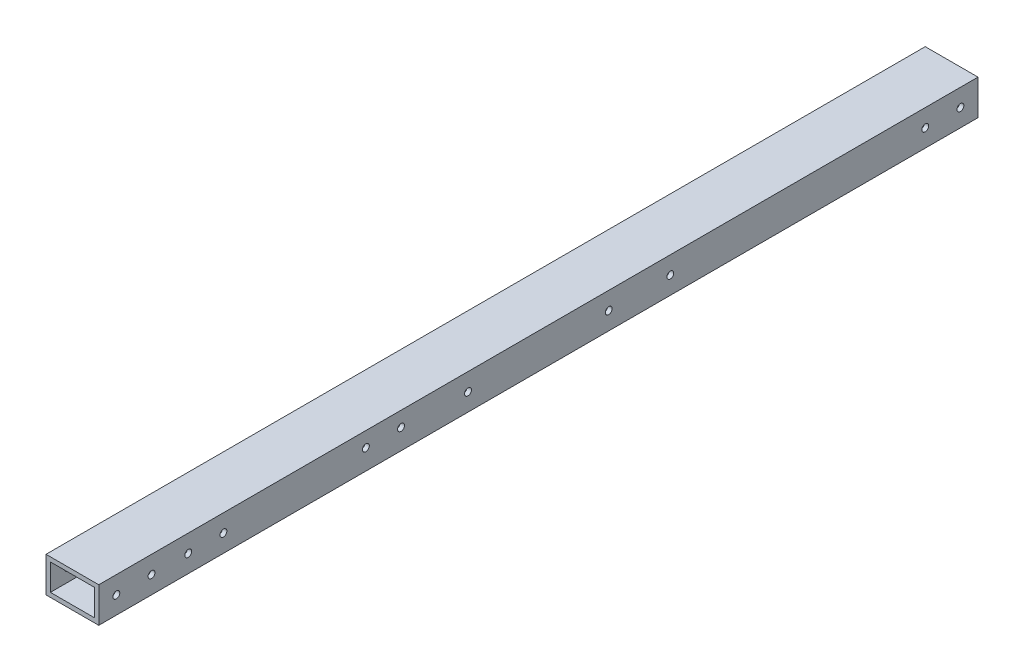
SolidWorks part; units mm, degrees
material "1060 Alloy"
ref_plane "Front Plane" through (0, 0, 0) normal (0, 0, 1) x (1, 0, 0)
ref_plane "Top Plane" through (0, 0, 0) normal (0, 1, 0) x (1, 0, 0)
ref_plane "Right Plane" through (0, 0, 0) normal (1, 0, 0) x (0, 0, -1)
sketch "Sketch1" plane through (0, 0, 0) normal (0, 0, 1) x (1, 0, 0)
  line L0 (-15.875, 9.525) -> (15.875, 9.525)
  line L2 (-19.05, 12.7) -> (19.05, 12.7)
  line L3 (-19.05, 12.7) -> (-19.05, -12.7)
  line L4 (-19.05, -12.7) -> (19.05, -12.7)
  line L5 (19.05, 12.7) -> (19.05, -12.7)
  line L10 (15.875, 9.525) -> (15.875, -9.525)
  line L11 (-15.875, -9.525) -> (15.875, -9.525)
  line L12 (-15.875, 9.525) -> (-15.875, -9.525)
  point P12 (0, 12.7)
  point P14 (19.05, 0)
  dimension "Wall Thickness" = 3.175
  dimension "Outside Width" = 38.1
  dimension "Outside Height" = 25.4
  dimension "Inside Height" = 19.05
  dimension "Inside Width" = 31.75
sketch "Sketch2" plane through (0, 0, 0) normal (1, 0, 0) x (0, 0, -1)
  line L0 (317.5, 0) -> (-317.5, 0)
  point P4 (0, 0)
  point P7 (-317.5, 0)
  point P10 (317.5, 0)
  dimension "Length" = 635
sketch "Sketch3" plane through (0, 0, 0) normal (0, 0, 1) x (1, 0, 0)
  line L21 (19.05, 12.7) -> (-19.05, 12.7)
  line L22 (19.05, -12.7) -> (19.05, 12.7)
  line L23 (-19.05, -12.7) -> (19.05, -12.7)
  line L24 (-19.05, 12.7) -> (-19.05, -12.7)
  line L25 (19.05, 12.7) -> (-19.05, 12.7)
  line L26 (19.05, -12.7) -> (19.05, 12.7)
  line L27 (-19.05, -12.7) -> (19.05, -12.7)
  line L28 (-19.05, 12.7) -> (-19.05, -12.7)
  line L29 (15.875, 9.525) -> (-15.875, 9.525)
  line L30 (15.875, -9.525) -> (15.875, 9.525)
  line L31 (-15.875, -9.525) -> (15.875, -9.525)
  line L32 (-15.875, 9.525) -> (-15.875, -9.525)
  line L33 (15.875, 9.525) -> (-15.875, 9.525)
  line L34 (15.875, -9.525) -> (15.875, 9.525)
  line L35 (-15.875, -9.525) -> (15.875, -9.525)
  line L36 (-15.875, 9.525) -> (-15.875, -9.525)
  dimension "D1" = 0
  dimension "D2" = 0
extrude "Boss-Extrude1" add sketch "Sketch3" along normal up to vertex (317.5 mm away) and the other way up to vertex (317.5 mm away) up to point (0, 0, 317.5) other way up to point (0, 0, -317.5)
sketch "Drawing Reference" plane through (0, 0, 0) normal (1, 0, 0) x (0, 0, -1)
  line L0 (-317.5, 0) -> (317.5, 0) construction
  line L1 (0, -12.7) -> (0, 12.7) construction
  line L2 (-317.5, -12.7) -> (317.5, -12.7) construction
  line L5 (-317.5, 12.7) -> (317.5, 12.7) construction
  point P7 (-290.068, 0)
  point P8 (290.068, 0)
  dimension "D1" = 27.432
sketch "Sketch4" plane through (-19.05, 0, 0) normal (-1, 0, 0) x (0, 0, 1)
  line L0 (-317.5, 0) -> (-304.8, 0)
  line L1 (-317.5, 12.7) -> (-317.5, -12.7) construction
  line L2 (-304.8, 0) -> (-279.4, 0)
  line L3 (317.5, 12.7) -> (317.5, -12.7) construction
  line L4 (317.5, 0) -> (304.8, 0)
  line L5 (304.8, 0) -> (279.4, 0)
  line L6 (0, 0) -> (50.8, 0) construction
  line L7 (0, 0) -> (-50.8, 0) construction
  point P11 (-304.8, 0)
  point P13 (-279.4, 0)
  point P14 (304.8, 0)
  point P15 (279.4, 0)
hole_wizard "#10 Clearance Hole2" positions "Sketch11" profile "Sketch12" hole size "#10" standard "ANSI Inch" end condition through all
sketch "Sketch11" plane through (-19.05, 0, 0) normal (-1, 0, 0) x (0, 0, 1)
  point P0 (-304.8, 0)
  point P3 (-279.4, 0)
  point P6 (279.4, 0)
  point P9 (304.8, 0)
sketch "Sketch12" plane through (-19.05, 0, -304.8) normal (0, 1, 0) x (0, 0, 1)
  line L0 (0, 0) -> (0, 38.1)
  line L1 (0, 38.1) -> (2.4892, 38.1)
  line L2 (2.4892, 38.1) -> (2.4892, 0)
  line L5 (2.4892, 0) -> (0, 0)
  line L11 (0, -6.35) -> (0, 107.95) construction
  dimension "Thru Hole Dia." = 4.9784
  dimension "Thru Hole Depth" = 38.1
hole_wizard "#10 Clearance Hole4" positions "Sketch14" profile "Sketch16" hole size "#10" standard "ANSI Inch" end condition through all
sketch "Sketch14" plane through (19.05, 0, 0) normal (1, 0, 0) x (0, 0, -1)
  point P33 (-252.857, 0)
  point P36 (-227.457, 0)
  point P42 (-124.587, 1.9434)
  point P45 (-99.187, 1.9434)
sketch "Sketch16" plane through (19.05, 0, 252.857) normal (0, 1, 0) x (0, 0, -1)
  line L0 (0, 0) -> (0, 38.1)
  line L1 (0, 38.1) -> (2.4892, 38.1)
  line L2 (2.4892, 38.1) -> (2.4892, 0)
  line L5 (2.4892, 0) -> (0, 0)
  line L11 (0, -6.35) -> (0, 107.95) construction
  dimension "Thru Hole Dia." = 4.9784
  dimension "Thru Hole Depth" = 38.1
hole_wizard "#10 Clearance Hole3" positions "Sketch20" profile "Sketch21" hole size "#10" standard "ANSI Inch" end condition through all
sketch "Sketch20" plane through (-19.05, 0, 0) normal (-1, 0, 0) x (0, 0, 1)
  point P0 (-50.8, 0)
  point P3 (50.8, 0)
sketch "Sketch21" plane through (-19.05, 0, -50.8) normal (0, 1, 0) x (0, 0, 1)
  line L0 (0, 0) -> (0, 38.1)
  line L1 (0, 38.1) -> (2.4892, 38.1)
  line L2 (2.4892, 38.1) -> (2.4892, 0)
  line L5 (2.4892, 0) -> (0, 0)
  line L11 (0, -6.35) -> (0, 107.95) construction
  dimension "Thru Hole Dia." = 4.9784
  dimension "Thru Hole Depth" = 38.1
sketch "Sketch22" plane through (19.05, 0, 0) normal (1, 0, 0) x (0, 0, -1)
  line L0 (50.8, 0) -> (95.25, 0) construction
hole_wizard "#10 Clearance Hole5" positions "Sketch23" profile "Sketch24" hole size "#10" standard "ANSI Inch" end condition through all
sketch "Sketch23" plane through (19.05, 0, 0) normal (1, 0, 0) x (0, 0, -1)
  point P0 (95.25, 0)
sketch "Sketch24" plane through (19.05, 0, -95.25) normal (0, 1, 0) x (0, 0, -1)
  line L0 (0, 0) -> (0, 38.1)
  line L1 (0, 38.1) -> (2.4892, 38.1)
  line L2 (2.4892, 38.1) -> (2.4892, 0)
  line L5 (2.4892, 0) -> (0, 0)
  line L11 (0, -6.35) -> (0, 107.95) construction
  dimension "Thru Hole Dia." = 4.9784
  dimension "Thru Hole Depth" = 38.1
equation "\"D1@Drawing Reference\"=\"Outside Width@Sketch1\" * 0.72"
